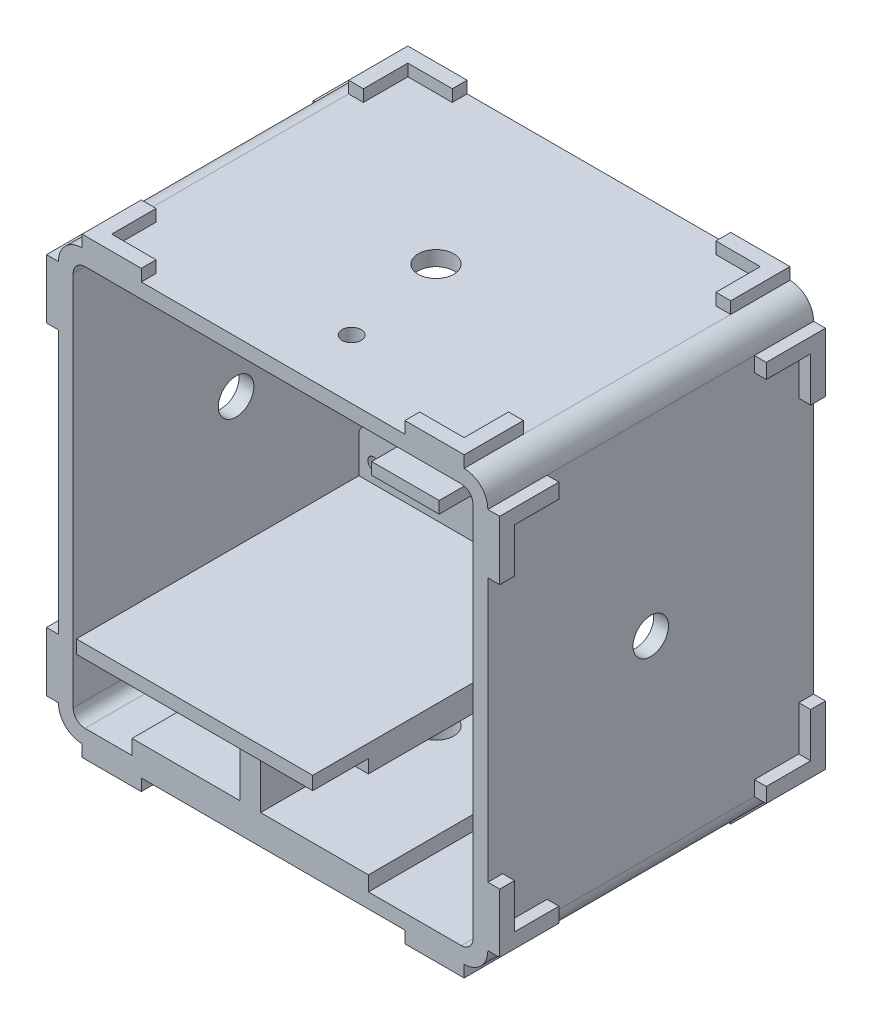
SolidWorks part; units mm, degrees
ref_plane "Front Plane" through (0, 0, 0) normal (0, 0, 1) x (1, 0, 0)
ref_plane "Top Plane" through (0, 0, 0) normal (0, 1, 0) x (1, 0, 0)
ref_plane "Right Plane" through (0, 0, 0) normal (1, 0, 0) x (0, 0, -1)
sketch "Sketch1" plane through (0, 0, 0) normal (0, 0, 1) x (1, 0, 0)
  line L0 (-33.75, -33.75) -> (33.75, -33.75) construction
  line L1 (-31.75, 33.75) -> (31.75, 33.75)
  line L2 (-33.75, 31.75) -> (-33.75, -31.75)
  line L3 (-31.75, -33.75) -> (31.75, -33.75)
  line L4 (33.75, 31.75) -> (33.75, -31.75)
  line L5 (-36.25, 32.25) -> (-36.25, -32.25)
  line L6 (33.75, 33.75) -> (33.75, -33.75) construction
  line L7 (-32.25, -36.25) -> (32.25, -36.25)
  line L8 (36.25, 32.25) -> (36.25, -32.25)
  line L9 (-32.25, 36.25) -> (32.25, 36.25)
  line L10 (-36.25, 36.25) -> (-36.25, -36.25) construction
  line L11 (-36.25, 36.25) -> (36.25, 36.25) construction
  line L12 (-33.75, 33.75) -> (33.75, 33.75) construction
  line L13 (-33.75, 33.75) -> (-33.75, -33.75) construction
  line L14 (-36.25, -36.25) -> (36.25, -36.25) construction
  line L15 (36.25, 36.25) -> (36.25, -36.25) construction
  line L16 (55, 0) -> (-55, 0) construction
  line L17 (0, -55) -> (0, 55) construction
  arc A0 (-36.25, 32.25) -> (-32.25, 36.25) centre (-32.25, 32.25) cw
  arc A1 (-31.75, 33.75) -> (-33.75, 31.75) centre (-31.75, 31.75) ccw
  arc A2 (-33.75, -31.75) -> (-31.75, -33.75) centre (-31.75, -31.75) ccw
  arc A3 (31.75, -33.75) -> (33.75, -31.75) centre (31.75, -31.75) ccw
  arc A4 (31.75, 33.75) -> (33.75, 31.75) centre (31.75, 31.75) cw
  arc A5 (-36.25, -32.25) -> (-32.25, -36.25) centre (-32.25, -32.25) ccw
  arc A6 (32.25, -36.25) -> (36.25, -32.25) centre (32.25, -32.25) ccw
  arc A7 (36.25, 32.25) -> (32.25, 36.25) centre (32.25, 32.25) ccw
  point P36 (-33.75, 0)
  point P39 (0, 33.75)
  dimension "D3" = 4
  dimension "D4" = 2
  dimension "D5" = 2
  dimension "D6" = 4
  dimension "D1" = 67.5
  dimension "D2" = 2.5
extrude "Boss-Extrude1" add sketch "Sketch1" along normal blind 55
sketch "Sketch2" plane through (0, 0, 0) normal (0, 0, 1) x (1, 0, 0)
  line L1 (-33.75, 33.75) -> (33.75, 33.75)
  line L2 (-33.75, 33.75) -> (-33.75, -33.75)
  line L3 (-33.75, -33.75) -> (33.75, -33.75)
  line L4 (33.75, 33.75) -> (33.75, -33.75)
extrude "Boss-Extrude2" add sketch "Sketch2" along normal blind 2.5
sketch "Sketch3" plane through (0, 0, 2.5) normal (0, 0, 1) x (1, 0, 0)
  line L0 (-4.38, 17.29) -> (-18.88, 12.29) construction
  line L1 (-19.88, 11.29) -> (-3.38, 11.29)
  line L2 (-18.88, 12.29) -> (-4.38, 12.29) construction
  line L3 (-18.88, 12.29) -> (-18.88, 17.29) construction
  line L4 (-18.88, 17.29) -> (-4.38, 17.29) construction
  line L5 (-4.38, 12.29) -> (-4.38, 17.29) construction
  line L6 (-3.38, 11.29) -> (-3.38, 18.29)
  line L7 (-19.88, 18.29) -> (-3.38, 18.29)
  line L8 (-19.88, 11.29) -> (-19.88, 18.29)
  line L9 (-36.25, 32.25) -> (-36.25, -32.25) construction
  line L10 (-3, -7) -> (3, -7) construction
  line L11 (-3, -7) -> (-3, 7) construction
  line L12 (-3, 7) -> (3, 7) construction
  line L13 (3, -7) -> (3, 7) construction
  line L14 (-3, -7) -> (3, 7) construction
  line L15 (-3, 7) -> (3, -7) construction
  line L16 (32.25, 36.25) -> (-32.25, 36.25) construction
  line L17 (-4, -8) -> (-4, 8)
  line L18 (-4, 8) -> (4, 8)
  line L19 (4, -8) -> (4, 8)
  line L20 (-4, -8) -> (4, -8)
  line L21 (-18.88, 17.29) -> (-4.38, 12.29) construction
  point P0 (0, 0)
  dimension "D2" = 6
  dimension "D3" = 14
  dimension "D5" = 14.5
  dimension "D6" = 5
  dimension "D7" = 16.37
  dimension "D8" = 23.96
  dimension "D1" = 1
  dimension "D4" = 1
extrude "Cut-Extrude1" cut sketch "Sketch3" against normal up to next
fillet "Fillet1" radius 1 8 edges at (-19.88, 11.29, 1.25) (-19.88, 18.29, 1.25) (-3.38, 18.29, 1.25) (-3.38, 11.29, 1.25) (4, -8, 1.25) (-4, -8, 1.25) (-4, 8, 1.25) (4, 8, 1.25)
sketch "Sketch4" plane through (0, 0, 0) normal (0, 0, -1) x (-1, 0, 0)
  line L0 (-32.25, 36.25) -> (32.25, 36.25) construction
  line L1 (-36.25, -32.25) -> (-36.25, 32.25) construction
  circle A0 centre (-28.75, 28.75) radius 1.5
  dimension "D3" = 3
  dimension "D1" = 7.5
  dimension "D2" = 7.5
extrude "Cut-Extrude2" cut sketch "Sketch4" against normal up to next
mirror "Mirror1" about plane through (0, 0, 0) normal (1, 0, 0) of "Cut-Extrude2"
mirror "Mirror2" about plane through (0, 0, 0) normal (0, 1, 0) of "Mirror1"
sketch "Sketch5" plane through (0, 0, 0) normal (1, 0, 0) x (0, 0, -1)
  line L0 (-14.7, 14) -> (-64.4, 14)
  line L1 (-16.7, 12) -> (-62.4, 12)
  line L2 (-16.7, 12) -> (-16.7, -12)
  line L3 (-16.7, -12) -> (-62.4, -12)
  line L5 (-64.4, 14) -> (-64.4, 12)
  line L6 (-14.7, -14) -> (-64.4, -14)
  line L7 (-14.7, 14) -> (-14.7, -14)
  line L8 (-62.4, 12) -> (-64.4, 12)
  line L9 (-62.4, -12) -> (-64.4, -12)
  line L10 (-64.4, -12) -> (-64.4, -14)
  line L11 (-62.4, 12) -> (-62.4, -12) construction
  line L12 (-64.4, 14) -> (-64.4, -14) construction
  line L13 (30.25, 0) -> (-30.25, 0) construction
  line L14 (-55, 32.25) -> (-55, -32.25) construction
  dimension "D1" = 45.7
  dimension "D2" = 24
  dimension "D4" = 12
  dimension "D5" = 9.4
  dimension "D3" = 2
extrude "Boss-Extrude3" add sketch "Sketch5" along normal blind 16.09 and the other way blind 23.81 separate body
sketch "Sketch6" plane through (0, 0, 64.4) normal (0, 0, 1) x (1, 0, 0)
  line L0 (-23.81, -14) -> (16.09, -14) construction
  line L1 (-23.81, -14) -> (16.09, -14)
  line L2 (-23.81, -14) -> (-23.81, -16.5)
  line L3 (-23.81, -16.5) -> (-5.61, -16.5)
  line L4 (16.09, -14) -> (16.09, -16.5)
  line L5 (-31.75, -33.75) -> (31.75, -33.75) construction
  line L6 (-23.81, -33.75) -> (16.09, -33.75)
  line L7 (-23.81, -33.75) -> (-23.81, -31.25)
  line L8 (-23.81, -31.25) -> (-5.61, -31.25)
  line L9 (16.09, -33.75) -> (16.09, -31.25)
  line L10 (-2.11, -16.5) -> (16.09, -16.5)
  line L12 (-5.61, -16.5) -> (-5.61, -31.25)
  line L14 (-2.11, -16.5) -> (-2.11, -31.25)
  line L15 (-2.11, -31.25) -> (16.09, -31.25)
  line L16 (-23.81, -12) -> (-23.81, -14) construction
  dimension "D1" = 2.5
  dimension "D2" = 2.5
  dimension "D3" = 39.9
  dimension "D4" = 39.9
  dimension "D5" = 3.5
  dimension "D6" = 18.2
  dimension "D7" = 18.2
extrude "Boss-Extrude4" add sketch "Sketch6" against normal blind 47
sketch "Sketch7" plane through (0, 0, 64.4) normal (0, 0, 1) x (1, 0, 0)
  line L0 (-23.81, -12) -> (-23.81, -16.5) construction
  line L1 (-23.81, -14.25) -> (16.09, -14.25)
  line L2 (-23.81, -14.25) -> (-23.81, -33.75)
  line L3 (-23.81, -33.75) -> (16.09, -33.75)
  line L4 (16.09, -14.25) -> (16.09, -33.75)
  line L5 (16.09, -33.75) -> (31.75, -33.75) construction
  line L6 (16.09, -33.75) -> (16.09, -31.25) construction
extrude "Cut-Extrude3" cut sketch "Sketch7" against normal blind 9.4
sketch "Sketch8" plane through (-23.81, 0, 0) normal (-1, 0, 0) x (0, 0, 1)
  line L0 (16.7, 12) -> (16.7, -12) construction
  line L1 (16.7, 12) -> (22.2, 12)
  line L2 (16.7, 12) -> (16.7, 6.5)
  line L3 (16.7, 6.5) -> (20.6, 6.5)
  line L4 (22.2, 12) -> (22.2, 8.1)
  arc A0 (20.6, 6.5) -> (22.2, 8.1) centre (20.6, 8.1) ccw
  circle A1 centre (19.7, 9) radius 1 construction
  circle A2 centre (19.7, 9) radius 1.8
  dimension "D1" = 1.6
  dimension "D4" = 3.6
  dimension "D5" = 2
  dimension "D2" = 5.5
  dimension "D3" = 5.5
  dimension "D6" = 3
  dimension "D7" = 3
extrude "Boss-Extrude5" [suppressed] add sketch "Sketch8" against normal blind 3
sketch "Sketch9" [suppressed] plane through (-15.56, 0, 0) normal (-1, 0, 0) x (0, 0, 1)
  circle A0 centre (22.3967, 9) radius 1
  circle A1 centre (22.3967, 9) radius 2
  dimension "D1" = 2
  dimension "D2" = 1
extrude "Boss-Extrude6" [suppressed] add sketch "Sketch9" along normal blind 1.5
ref_plane "Plane1" through (-9.11, 0, 0) normal (-1, 0, 0) x (0, 0, 1)
mirror "Mirror3" [suppressed] about plane through (-9.11, 0, 0) normal (-1, 0, 0)
ref_plane "Plane2" through (0, 0, 0) normal (0, 1, 0) x (1, 0, 0)
mirror "Mirror4" [suppressed] about plane through (0, 0, 0) normal (0, 1, 0)
sketch "Sketch10" [suppressed] plane through (-36.25, 0, 0) normal (-1, 0, 0) x (0, 0, 1)
  circle A0 centre (22.3967, 9) radius 1.5
  circle A1 centre (22.3967, -9) radius 1.5
  dimension "D1" = 3
  dimension "D2" = 3
extrude "Cut-Extrude4" [suppressed] cut sketch "Sketch10" against normal through all
sketch "Sketch12" plane through (0, 36.25, 0) normal (0, 1, 0) x (1, 0, 0)
  line L0 (-32.25, -55) -> (-32.25, 0) construction
  line L1 (32.25, -55) -> (29.75, -55)
  line L2 (32.25, -55) -> (32.25, -45)
  line L3 (32.25, -45) -> (29.75, -45)
  line L4 (29.75, -52.5) -> (29.75, -45)
  line L5 (32.25, -55) -> (22.25, -55)
  line L6 (32.25, -55) -> (32.25, -52.5)
  line L7 (29.75, -52.5) -> (22.25, -52.5)
  line L8 (22.25, -55) -> (22.25, -52.5)
  line L10 (-32.25, 0) -> (-32.25, -10)
  line L11 (-32.25, -10) -> (-29.75, -10)
  line L12 (-29.75, -2.5) -> (-29.75, -10)
  line L13 (-32.25, 0) -> (-22.25, 0)
  line L15 (-29.75, -2.5) -> (-22.25, -2.5)
  line L16 (-22.25, 0) -> (-22.25, -2.5)
  line M6 (-32.25, -55) -> (32.25, -55)
  line M7 (32.25, -55) -> (32.25, 0)
  dimension "D1" = 2.5
  dimension "D2" = 10
  dimension "D3" = 2.5
  dimension "D4" = 10
  dimension "D5" = 2.5
extrude "Boss-Extrude7" add sketch "Sketch12" along normal blind 2 contours L8 L2 L3 L4 L7 M6 M7 | L10 L11 L12 L15 L16 L13 region at (31, 36.25, 54.8586)
sketch "Sketch13" plane through (0, 0, 0) normal (0, 0, -1) x (-1, 0, 0)
  line L3 (-33.75, 21.25) -> (-25.25, 21.25)
  line L4 (-21.25, 33.75) -> (-21.25, 25.25)
  line L6 (0, 35.42) -> (0, -35.42) construction
  line L8 (21.25, 33.75) -> (21.25, 25.25)
  line L9 (33.75, 21.25) -> (25.25, 21.25)
  line L12 (35.42, 0) -> (-35.42, 0) construction
  line L17 (33.75, -21.25) -> (25.25, -21.25)
  line L18 (21.25, -33.75) -> (21.25, -25.25)
  line L19 (-21.25, -33.75) -> (-21.25, -25.25)
  line L20 (-33.75, -21.25) -> (-25.25, -21.25)
  line L27 (-33.75, 21.25) -> (-33.75, -21.25)
  line L29 (33.75, 21.25) -> (33.75, -21.25)
  line L34 (-21.25, 33.75) -> (21.25, 33.75)
  line L36 (-21.25, -33.75) -> (21.25, -33.75)
  arc A2 (-25.25, 21.25) -> (-21.25, 25.25) centre (-25.25, 25.25) ccw
  arc A4 (25.25, 21.25) -> (21.25, 25.25) centre (25.25, 25.25) cw
  arc A7 (25.25, -21.25) -> (21.25, -25.25) centre (25.25, -25.25) ccw
  arc A8 (-25.25, -21.25) -> (-21.25, -25.25) centre (-25.25, -25.25) cw
  dimension "D3" = 4
extrude "Cut-Extrude6" cut sketch "Sketch13" against normal up to next and the other way through all
sketch "Sketch14" plane through (0, 0, 14.7) normal (0, 0, -1) x (-1, 0, 0)
  line L1 (23.81, 14) -> (9.11, 14)
  line L2 (23.81, 14) -> (23.81, 12)
  line L3 (23.81, 12) -> (9.11, 12)
  line L4 (9.11, 14) -> (9.11, 12)
  dimension "D1" = 14.7
  dimension "D2" = 2
extrude "Cut-Extrude7" cut sketch "Sketch14" against normal up to next
sketch "Sketch15" plane through (0, 36.25, 0) normal (0, 1, 0) x (1, 0, 0)
  line L0 (22.25, -55) -> (-32.25, -55) construction
  line L1 (33.75, -55) -> (33.75, -2.5) construction
  circle A0 centre (3.25, -45) radius 1.6
  dimension "D1" = 3.2
  dimension "D2" = 10
  dimension "D3" = 30.5
extrude "Cut-Extrude8" cut sketch "Sketch15" against normal up to surface (2.5 mm away) and the other way through all up to face at (0, 33.75, 15)
sketch "Sketch16" plane through (-33.75, 0, 0) normal (1, 0, 0) x (0, 0, -1)
  line L2 (-16, 32.15) -> (-16, 29.65)
  line L7 (-16, 29.65) -> (-8.5, 29.65)
  line L9 (-16, 32.15) -> (-8.5, 32.15)
  line L10 (-8.5, 29.65) -> (-8.5, 32.15)
  line L12 (0, -32.25) -> (0, 32.25) construction
  dimension "D1" = 7.5
  dimension "D3" = 16
extrude "Boss-Extrude8" add sketch "Sketch16" along normal blind 7
sketch "Sketch11" plane through (0, 14, 0) normal (0, 1, 0) x (1, 0, 0)
  line L0 (1.19, -39.55) -> (12.59, -39.55)
  line L1 (-23.81, -64.4) -> (1.19, -64.4)
  line L2 (-23.81, -64.4) -> (-23.81, -14.7)
  line L3 (-23.81, -14.7) -> (1.19, -14.7)
  line L4 (1.19, -39.55) -> (1.19, -14.7)
  line L5 (16.09, -64.4) -> (12.59, -64.4)
  line L6 (16.09, -64.4) -> (16.09, -14.7)
  line L7 (16.09, -14.7) -> (12.59, -14.7)
  line L8 (12.59, -39.55) -> (12.59, -14.7)
  line L9 (1.19, -64.4) -> (12.59, -64.4)
  dimension "D1" = 25
  dimension "D2" = 49.7
  dimension "D3" = 3.5
extrude "Cut-Extrude5" cut sketch "Sketch11" against normal blind 2
sketch "Sketch17" plane through (0, 0, 14.7) normal (0, 0, -1) x (-1, 0, 0)
  line L0 (-16.09, -14) -> (-16.09, 12) construction
  line L1 (-1.19, 12) -> (23.81, 12) construction
  line L2 (23.81, -14) -> (23.81, 12) construction
  circle A0 centre (-13.59, 9) radius 1
  circle A1 centre (-13.59, -9) radius 1
  circle A2 centre (21.31, -9) radius 1
  dimension "D1" = 2
  dimension "D2" = 2.5
  dimension "D3" = 3
  dimension "D4" = 2.5
  dimension "D6" = 18
extrude "Cut-Extrude9" cut sketch "Sketch17" against normal up to next
sketch "Sketch19" plane through (0, 36.25, 0) normal (0, 1, 0) x (1, 0, 0)
  line L0 (32.25, -55) -> (-32.25, 0) construction
  line L1 (-32.25, 0) -> (-22.25, 0) construction
  line L2 (32.25, 0) -> (-32.25, -55) construction
  line L3 (32.25, -45) -> (32.25, 0) construction
  line L4 (32.25, 0) -> (-22.25, 0) construction
  line L5 (-32.25, 0) -> (-32.25, -10) construction
  line L6 (-32.25, 0) -> (-32.25, -10) construction
  circle A0 centre (0, -27.5) radius 3
  dimension "D1" = 6
extrude "Cut-Extrude10" cut sketch "Sketch19" against normal blind 2.5
sketch "Sketch20" plane through (36.25, 0, -36.25) normal (-1, 0, 0) x (0, 0, 1)
  line L0 (36.25, -32.25) -> (36.25, 32.25) construction
  line L1 (36.25, -32.25) -> (36.25, -22.25)
  line L2 (36.25, -32.25) -> (46.25, -32.25)
  line L3 (46.25, -32.25) -> (46.25, -29.75)
  line L4 (38.75, -29.75) -> (46.25, -29.75)
  line L5 (36.25, -32.25) -> (36.25, -22.25)
  line L7 (38.75, -29.75) -> (38.75, -22.25)
  line L8 (36.25, -22.25) -> (38.75, -22.25)
  line L10 (91.25, 32.25) -> (81.25, 32.25)
  line L11 (81.25, 32.25) -> (81.25, 29.75)
  line L12 (88.75, 29.75) -> (81.25, 29.75)
  line L13 (91.25, 32.25) -> (91.25, 22.25)
  line L15 (88.75, 29.75) -> (88.75, 22.25)
  line L16 (91.25, 22.25) -> (88.75, 22.25)
  line M25 (36.25, -32.25) -> (36.25, 32.25)
  line M26 (36.25, 32.25) -> (91.25, 32.25)
  line M27 (91.25, 32.25) -> (91.25, -32.25)
  line M28 (91.25, -32.25) -> (36.25, -32.25)
  dimension "D1" = 2.5
  dimension "D2" = 10
  dimension "D3" = 2.5
  dimension "D4" = 10
  dimension "D5" = 2.5
  dimension "D6" = 55
  dimension "D7" = 64.5
  dimension "D8" = 10
  dimension "D9" = 7.5
  dimension "D10" = 7.5
extrude "Boss-Extrude9" add sketch "Sketch20" against normal blind 2 contours L16 L15 L12 L11 M27 M26 | L8 L7 L4 L3 M25 M28 region at (36.25, -27.25, 0.1414) region at (36.25, 32.1086, 50)
ref_axis "Axis1" through (0, 0, 67.62) along (0, 0, -1)
pattern_circular "CirPattern1" count 4 every 90 about axis through (0, 0, 67.62) along (0, 0, -1) of "Boss-Extrude7", "Cut-Extrude10"
pattern_circular "CirPattern2" count 4 every 90 about axis through (0, 0, 67.62) along (0, 0, -1) of "Boss-Extrude9"
sketch "Sketch21" plane through (0, -33.75, 0) normal (0, -1, 0) x (1, 0, 0)
  line L0 (-2.11, 25.3674) -> (-2.11, 29.6326)
  arc A0 (-2.11, 25.3674) -> (-2.11, 29.6326) centre (0, 27.5) ccw
extrude "Cut-Extrude11" cut sketch "Sketch21" against normal blind 2.5
sketch "Sketch22" plane through (0, 0, 14.7) normal (0, 0, -1) x (-1, 0, 0)
  line L0 (-1.19, 12) -> (23.81, 12) construction
  line L1 (18.81, 12) -> (23.81, 12)
  line L2 (18.81, 12) -> (18.81, -4)
  line L3 (18.81, -4) -> (23.81, -4)
  line L4 (23.81, 12) -> (23.81, -4)
  line L5 (23.81, -14) -> (23.81, 12) construction
  line L6 (23.81, -14) -> (-16.09, -14) construction
  point P8 (18.8684, -5.1343)
  dimension "D1" = 5
  dimension "D2" = 10
extrude "Cut-Extrude12" cut sketch "Sketch22" against normal up to next
fillet "Fillet2" radius 2 1 edges at (-23.81, -4, 15.7)
